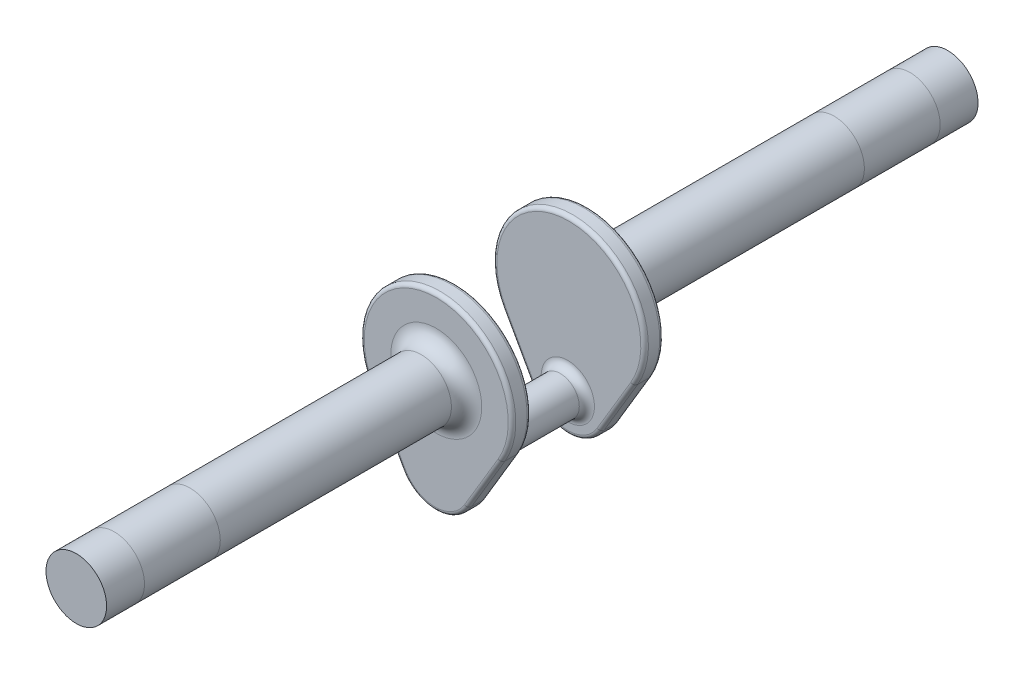
SolidWorks part; units mm, degrees
material "Alloy Steel"
ref_plane "Front" through (0, 0, 0) normal (0, 0, 1) x (1, 0, 0)
ref_plane "Top" through (0, 0, 0) normal (0, 1, 0) x (1, 0, 0)
ref_plane "Right" through (0, 0, 0) normal (1, 0, 0) x (0, 0, -1)
sketch "Sketch1" plane through (0, 0, 0) normal (0, 0, 1) x (1, 0, 0)
  line L1 (-22.1747, -12.3872) -> (-11.4456, -31.5936)
  line L2 (21.8165, -13.0077) -> (10.55, -31.9039)
  arc A0 (21.8165, -13.0077) -> (-22.1747, -12.3872) centre (0, 0) ccw
  arc A1 (-11.4456, -31.5936) -> (10.55, -31.9039) centre (-0.3582, -25.4) ccw
  dimension "D1" = 25.4
  dimension "D2" = 12.7
  dimension "D3" = 25.4
extrude "Extrude1" add sketch "Sketch1" along normal blind 6.35
sketch "Sketch2" plane through (0, 0, 0) normal (0, 0, -1) x (-1, 0, 0)
  circle A0 centre (0, 0) radius 10.1604
extrude "Extrude2" add sketch "Sketch2" along normal blind 120.65
sketch "Sketch3" plane through (0, 0, 6.35) normal (0, 0, 1) x (1, 0, 0)
  circle A2 centre (-0.3582, -25.4) radius 6.3892
extrude "Extrude4" add sketch "Sketch3" along normal blind 19.05
fillet "Fillet1" radius 2.54 1 edges at (6.0309, -25.4, 6.35)
fillet "Fillet2" radius 5.08 1 edges at (10.1604, 0, 0)
fillet "Fillet3" radius 1.27 8 edges at (16.1833, -22.4558, 6.35) (-0.5373, -38.0987, 6.35) (-16.8101, -21.9904, 6.35) (16.1833, -22.4558, 0) (-0.5373, -38.0987, 0) (-16.8101, -21.9904, 0) (0.3582, 25.3975, 6.35) (0.3582, 25.3975, 0)
ref_plane "Plane3" through (0, 0, -107.95) normal (0, 0, -1) x (-1, 0, 0)
ref_plane "Plane4" through (0, 0, -82.55) normal (0, 0, -1) x (-1, 0, 0)
sketch "Sketch5" plane through (0, 0, 0) normal (0, 1, 0) x (1, 0, 0)
  line L0 (-48.6529, 82.55) -> (48.6529, 82.55)
  line L1 (11.1765, 82.55) -> (-11.1765, 82.55) construction
split line "Split Line4"
sketch "Sketch6" plane through (0, 0, 0) normal (0, 1, 0) x (1, 0, 0)
  line L0 (-27.9735, 107.95) -> (32.6427, 107.95)
  line L1 (11.1765, 107.95) -> (-11.1765, 107.95) construction
split line "Split Line5"
mirror "Mirror2" about plane through (-0.3582, -25.4, 25.4) normal (0, 0, 1) of bodies 103
ref_axis "Axis1" through (0, 0, 133.35) along (0, 0, -1)
sketch "Sketch7" plane through (0, 0, 0) normal (0, 1, 0) x (1, 0, 0)
  line L0 (0, -146.05) -> (0, 95.25)
  line L1 (0, -133.35) -> (0, -55.88) construction
  line L2 (-10.1604, -158.75) -> (10.1604, -158.75) construction
  line L3 (-10.1604, 107.95) -> (10.1604, 107.95) construction
  dimension "D1" = 12.7
  dimension "D2" = 12.7
